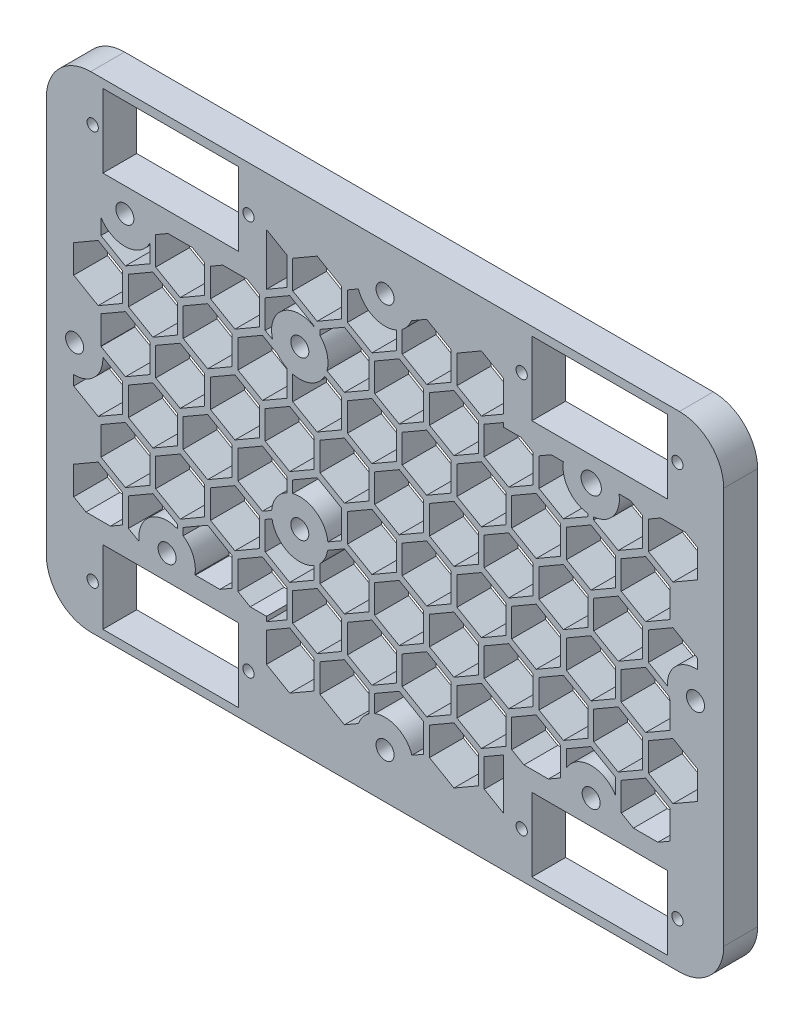
SolidWorks part; units mm, degrees
material "Pin"
ref_plane "Plan de face" through (0, 0, 0) normal (0, 0, 1) x (1, 0, 0)
ref_plane "Plan de dessus" through (0, 0, 0) normal (0, 1, 0) x (1, 0, 0)
ref_plane "Plan de droite" through (0, 0, 0) normal (1, 0, 0) x (0, 0, -1)
sketch "Esquisse1" plane through (0, 0, 0) normal (0, 0, 1) x (1, 0, 0)
  line L0 (-60, -35.145) -> (-60, 35.145)
  line L1 (-52.145, 43) -> (52.145, 43)
  line L2 (-55, 0) -> (-60, 0) construction
  line L3 (55, 0) -> (55, 42.4628) construction
  line L4 (60, -35.145) -> (60, 35.145)
  line L5 (-52.145, -43) -> (52.145, -43)
  line L6 (55, 0) -> (55, -42.4628) construction
  line L7 (-55, 0) -> (-55, -42.4628) construction
  line L8 (-55, 0) -> (-55, 42.4628) construction
  line L9 (55, 0) -> (60, 0) construction
  line L10 (0, -35) -> (59.9987, -35) construction
  line L11 (0, -35) -> (-59.9987, -35) construction
  line L12 (55, 0) -> (60, 0) construction
  line L13 (0, 35) -> (59.9987, 35) construction
  line L14 (0, 35) -> (-59.9987, 35) construction
  arc A0 (60, -35.145) -> (52.145, -43) centre (52.145, -35.145) cw
  arc A1 (-52.145, -43) -> (-60, -35.145) centre (-52.145, -35.145) cw
  circle A2 centre (0, 35) radius 1.6
  circle A3 centre (0, -35) radius 1.6
  arc A4 (-52.145, 43) -> (-60, 35.145) centre (-52.145, 35.145) ccw
  arc A5 (52.145, 43) -> (60, 35.145) centre (52.145, 35.145) cw
  circle A8 centre (-55, 0) radius 1.6
  circle A14 centre (55, 0) radius 1.6
  dimension "D6" = 8
  dimension "D7" = 3.2
  dimension "D8" = 3.2
  dimension "D10" = 120
  dimension "D5" = 5
  dimension "D4" = 86
  dimension "D36" = 3.2
  dimension "D2" = 3.2
extrude "plaque" add sketch "Esquisse1" along normal blind 6 contours L4 L1 L0 A1 L5 A0 region at (0, 0, 0)
sketch "Esquisse3" plane through (0, 0, 0) normal (0, 0, 1) x (1, 0, 0)
  line L0 (0, 0) -> (0, 43.3988) construction
  line L1 (0, 0) -> (-88.517, 0) construction
  line L2 (-51.8, 35) -> (-24.2, 35) construction
  line L3 (26, 28.5) -> (26, 41.5)
  line L4 (-50, 28.5) -> (-50, 41.5)
  line L5 (-50, 28.5) -> (-26, 28.5)
  line L6 (-26, 28.5) -> (-26, 41.5)
  line L7 (-50, 41.5) -> (-26, 41.5)
  line L8 (50, -28.5) -> (26, -28.5)
  line L9 (50, -28.5) -> (50, -41.5)
  line L10 (50, 41.5) -> (26, 41.5)
  line L11 (50, 28.5) -> (50, 41.5)
  line L12 (50, 28.5) -> (26, 28.5)
  line L13 (50, -41.5) -> (26, -41.5)
  line L14 (26, -28.5) -> (26, -41.5)
  line L15 (-51.8, -35) -> (-24.2, -35) construction
  line L16 (-50, -41.5) -> (-26, -41.5)
  line L17 (-26, -28.5) -> (-26, -41.5)
  line L18 (-50, -28.5) -> (-26, -28.5)
  line L19 (-50, -28.5) -> (-50, -41.5)
  circle A0 centre (-51.8, 35) radius 1
  circle A1 centre (-24.2, 35) radius 1
  circle A2 centre (51.8, 35) radius 1
  circle A3 centre (24.2, 35) radius 1
  circle A4 centre (24.2, -35) radius 1
  circle A5 centre (51.8, -35) radius 1
  circle A6 centre (-24.2, -35) radius 1
  circle A7 centre (-51.8, -35) radius 1
  point P3 (-50, 35)
  point P8 (-38, 35)
  point P37 (-26, 35)
  point P40 (-38, -35)
  dimension "D2" = 2
  dimension "D1" = 27.6
  dimension "D3" = 13
  dimension "D4" = 24
  dimension "D5" = 38
  dimension "D6" = 35
  dimension "D7" = 90
  dimension "D8" = 1.8
extrude "MIP_SERVO" cut sketch "Esquisse3" along normal through all
sketch "Sketch1" plane through (0, 0, 0) normal (0, 0, -1) x (-1, 0, 0)
  line L0 (-60, -35.145) -> (-60, 35.145) construction
  line L1 (-55.3301, 23.75) -> (-55.3301, 18.75)
  line L2 (-55.3301, 18.75) -> (-51, 16.25)
  line L3 (-51, 16.25) -> (-46.6699, 18.75)
  line L4 (-46.6699, 18.75) -> (-46.6699, 23.75)
  line L5 (-46.6699, 23.75) -> (-51, 26.25)
  line L6 (-51, 26.25) -> (-55.3301, 23.75)
  line L7 (52.145, 43) -> (-52.145, 43) construction
  line L8 (-50.5, 32.25) -> (-50.5, 27.25)
  line L9 (-50.5, 27.25) -> (-46.1699, 24.75)
  line L10 (-46.1699, 24.75) -> (-41.8397, 27.25)
  line L11 (-41.8397, 27.25) -> (-41.8397, 32.25)
  line L12 (-41.8397, 32.25) -> (-46.1699, 34.75)
  line L13 (-46.1699, 34.75) -> (-50.5, 32.25)
  line L14 (-45.6301, 23.75) -> (-45.6301, 18.75)
  line L15 (-45.6301, 18.75) -> (-41.3, 16.25)
  line L16 (-41.3, 16.25) -> (-36.9699, 18.75)
  line L17 (-36.9699, 18.75) -> (-36.9699, 23.75)
  line L18 (-36.9699, 23.75) -> (-41.3, 26.25)
  line L19 (-41.3, 26.25) -> (-45.6301, 23.75)
  line L20 (-40.8, 32.25) -> (-40.8, 27.25)
  line L21 (-40.8, 27.25) -> (-36.4699, 24.75)
  line L22 (-36.4699, 24.75) -> (-32.1397, 27.25)
  line L23 (-32.1397, 27.25) -> (-32.1397, 32.25)
  line L24 (-32.1397, 32.25) -> (-36.4699, 34.75)
  line L25 (-36.4699, 34.75) -> (-40.8, 32.25)
  line L26 (-35.9301, 23.75) -> (-35.9301, 18.75)
  line L27 (-35.9301, 18.75) -> (-31.6, 16.25)
  line L28 (-31.6, 16.25) -> (-27.2699, 18.75)
  line L29 (-27.2699, 18.75) -> (-27.2699, 23.75)
  line L30 (-27.2699, 23.75) -> (-31.6, 26.25)
  line L31 (-31.6, 26.25) -> (-35.9301, 23.75)
  line L32 (-31.1, 32.25) -> (-31.1, 27.25)
  line L33 (-31.1, 27.25) -> (-26.7699, 24.75)
  line L34 (-26.7699, 24.75) -> (-22.4397, 27.25)
  line L35 (-22.4397, 27.25) -> (-22.4397, 32.25)
  line L36 (-22.4397, 32.25) -> (-26.7699, 34.75)
  line L37 (-26.7699, 34.75) -> (-31.1, 32.25)
  line L38 (-26.2301, 23.75) -> (-26.2301, 18.75)
  line L39 (-26.2301, 18.75) -> (-21.9, 16.25)
  line L40 (-21.9, 16.25) -> (-17.5699, 18.75)
  line L41 (-17.5699, 18.75) -> (-17.5699, 23.75)
  line L42 (-17.5699, 23.75) -> (-21.9, 26.25)
  line L43 (-21.9, 26.25) -> (-26.2301, 23.75)
  line L44 (-21.4, 32.25) -> (-21.4, 27.25)
  line L45 (-21.4, 27.25) -> (-17.0699, 24.75)
  line L46 (-17.0699, 24.75) -> (-12.7397, 27.25)
  line L47 (-12.7397, 27.25) -> (-12.7397, 32.25)
  line L48 (-12.7397, 32.25) -> (-17.0699, 34.75)
  line L49 (-17.0699, 34.75) -> (-21.4, 32.25)
  line L50 (-16.5301, 23.75) -> (-16.5301, 18.75)
  line L51 (-16.5301, 18.75) -> (-12.2, 16.25)
  line L52 (-12.2, 16.25) -> (-7.8699, 18.75)
  line L53 (-7.8699, 18.75) -> (-7.8699, 23.75)
  line L54 (-7.8699, 23.75) -> (-12.2, 26.25)
  line L55 (-12.2, 26.25) -> (-16.5301, 23.75)
  line L56 (-11.7, 32.25) -> (-11.7, 27.25)
  line L57 (-11.7, 27.25) -> (-7.3699, 24.75)
  line L58 (-7.3699, 24.75) -> (-3.0397, 27.25)
  line L59 (-3.0397, 27.25) -> (-3.0397, 32.25)
  line L60 (-3.0397, 32.25) -> (-7.3699, 34.75)
  line L61 (-7.3699, 34.75) -> (-11.7, 32.25)
  line L62 (-6.8301, 23.75) -> (-6.8301, 18.75)
  line L63 (-6.8301, 18.75) -> (-2.5, 16.25)
  line L64 (-2.5, 16.25) -> (1.8301, 18.75)
  line L65 (1.8301, 18.75) -> (1.8301, 23.75)
  line L66 (1.8301, 23.75) -> (-2.5, 26.25)
  line L67 (-2.5, 26.25) -> (-6.8301, 23.75)
  line L68 (-2, 32.25) -> (-2, 27.25)
  line L69 (-2, 27.25) -> (2.3301, 24.75)
  line L70 (2.3301, 24.75) -> (6.6603, 27.25)
  line L71 (6.6603, 27.25) -> (6.6603, 32.25)
  line L72 (6.6603, 32.25) -> (2.3301, 34.75)
  line L73 (2.3301, 34.75) -> (-2, 32.25)
  line L74 (2.8699, 23.75) -> (2.8699, 18.75)
  line L75 (2.8699, 18.75) -> (7.2, 16.25)
  line L76 (7.2, 16.25) -> (11.5301, 18.75)
  line L77 (11.5301, 18.75) -> (11.5301, 23.75)
  line L78 (11.5301, 23.75) -> (7.2, 26.25)
  line L79 (7.2, 26.25) -> (2.8699, 23.75)
  line L80 (7.7, 32.25) -> (7.7, 27.25)
  line L81 (7.7, 27.25) -> (12.0301, 24.75)
  line L82 (12.0301, 24.75) -> (16.3603, 27.25)
  line L83 (16.3603, 27.25) -> (16.3603, 32.25)
  line L84 (16.3603, 32.25) -> (12.0301, 34.75)
  line L85 (12.0301, 34.75) -> (7.7, 32.25)
  line L86 (12.5699, 23.75) -> (12.5699, 18.75)
  line L87 (12.5699, 18.75) -> (16.9, 16.25)
  line L88 (16.9, 16.25) -> (21.2301, 18.75)
  line L89 (21.2301, 18.75) -> (21.2301, 23.75)
  line L90 (21.2301, 23.75) -> (16.9, 26.25)
  line L91 (16.9, 26.25) -> (12.5699, 23.75)
  line L92 (17.4, 32.25) -> (17.4, 27.25)
  line L93 (17.4, 27.25) -> (21.7301, 24.75)
  line L94 (21.7301, 24.75) -> (26.0603, 27.25)
  line L95 (26.0603, 27.25) -> (26.0603, 32.25)
  line L96 (26.0603, 32.25) -> (21.7301, 34.75)
  line L97 (21.7301, 34.75) -> (17.4, 32.25)
  line L98 (22.2699, 23.75) -> (22.2699, 18.75)
  line L99 (22.2699, 18.75) -> (26.6, 16.25)
  line L100 (26.6, 16.25) -> (30.9301, 18.75)
  line L101 (30.9301, 18.75) -> (30.9301, 23.75)
  line L102 (30.9301, 23.75) -> (26.6, 26.25)
  line L103 (26.6, 26.25) -> (22.2699, 23.75)
  line L104 (27.1, 32.25) -> (27.1, 27.25)
  line L105 (27.1, 27.25) -> (31.4301, 24.75)
  line L106 (31.4301, 24.75) -> (35.7603, 27.25)
  line L107 (35.7603, 27.25) -> (35.7603, 32.25)
  line L108 (35.7603, 32.25) -> (31.4301, 34.75)
  line L109 (31.4301, 34.75) -> (27.1, 32.25)
  line L110 (31.9699, 23.75) -> (31.9699, 18.75)
  line L111 (31.9699, 18.75) -> (36.3, 16.25)
  line L112 (36.3, 16.25) -> (40.6301, 18.75)
  line L113 (40.6301, 18.75) -> (40.6301, 23.75)
  line L114 (40.6301, 23.75) -> (36.3, 26.25)
  line L115 (36.3, 26.25) -> (31.9699, 23.75)
  line L116 (36.8, 32.25) -> (36.8, 27.25)
  line L117 (36.8, 27.25) -> (41.1301, 24.75)
  line L118 (41.1301, 24.75) -> (45.4603, 27.25)
  line L119 (45.4603, 27.25) -> (45.4603, 32.25)
  line L120 (45.4603, 32.25) -> (41.1301, 34.75)
  line L121 (41.1301, 34.75) -> (36.8, 32.25)
  line L122 (41.6699, 23.75) -> (41.6699, 18.75)
  line L123 (41.6699, 18.75) -> (46, 16.25)
  line L124 (46, 16.25) -> (50.3301, 18.75)
  line L125 (50.3301, 18.75) -> (50.3301, 23.75)
  line L126 (50.3301, 23.75) -> (46, 26.25)
  line L127 (46, 26.25) -> (41.6699, 23.75)
  line L128 (46.5, 32.25) -> (46.5, 27.25)
  line L129 (46.5, 27.25) -> (50.8301, 24.75)
  line L130 (50.8301, 24.75) -> (55.1603, 27.25)
  line L131 (55.1603, 27.25) -> (55.1603, 32.25)
  line L132 (55.1603, 32.25) -> (50.8301, 34.75)
  line L133 (50.8301, 34.75) -> (46.5, 32.25)
  line L134 (-45.6301, 6.75) -> (-45.6301, 1.75)
  line L135 (-45.6301, 1.75) -> (-41.3, -0.75)
  line L136 (-41.3, -0.75) -> (-36.9699, 1.75)
  line L137 (-36.9699, 1.75) -> (-36.9699, 6.75)
  line L138 (-36.9699, 6.75) -> (-41.3, 9.25)
  line L139 (-41.3, 9.25) -> (-45.6301, 6.75)
  line L140 (-40.8, 15.25) -> (-40.8, 10.25)
  line L141 (-40.8, 10.25) -> (-36.4699, 7.75)
  line L142 (-36.4699, 7.75) -> (-32.1397, 10.25)
  line L143 (-32.1397, 10.25) -> (-32.1397, 15.25)
  line L144 (-32.1397, 15.25) -> (-36.4699, 17.75)
  line L145 (-36.4699, 17.75) -> (-40.8, 15.25)
  line L146 (-35.9301, 6.75) -> (-35.9301, 1.75)
  line L147 (-35.9301, 1.75) -> (-31.6, -0.75)
  line L148 (-31.6, -0.75) -> (-27.2699, 1.75)
  line L149 (-27.2699, 1.75) -> (-27.2699, 6.75)
  line L150 (-27.2699, 6.75) -> (-31.6, 9.25)
  line L151 (-31.6, 9.25) -> (-35.9301, 6.75)
  line L152 (-31.1, 15.25) -> (-31.1, 10.25)
  line L153 (-31.1, 10.25) -> (-26.7699, 7.75)
  line L154 (-26.7699, 7.75) -> (-22.4397, 10.25)
  line L155 (-22.4397, 10.25) -> (-22.4397, 15.25)
  line L156 (-22.4397, 15.25) -> (-26.7699, 17.75)
  line L157 (-26.7699, 17.75) -> (-31.1, 15.25)
  line L158 (-26.2301, 6.75) -> (-26.2301, 1.75)
  line L159 (-26.2301, 1.75) -> (-21.9, -0.75)
  line L160 (-21.9, -0.75) -> (-17.5699, 1.75)
  line L161 (-17.5699, 1.75) -> (-17.5699, 6.75)
  line L162 (-17.5699, 6.75) -> (-21.9, 9.25)
  line L163 (-21.9, 9.25) -> (-26.2301, 6.75)
  line L164 (-21.4, 15.25) -> (-21.4, 10.25)
  line L165 (-21.4, 10.25) -> (-17.0699, 7.75)
  line L166 (-17.0699, 7.75) -> (-12.7397, 10.25)
  line L167 (-12.7397, 10.25) -> (-12.7397, 15.25)
  line L168 (-12.7397, 15.25) -> (-17.0699, 17.75)
  line L169 (-17.0699, 17.75) -> (-21.4, 15.25)
  line L170 (-16.5301, 6.75) -> (-16.5301, 1.75)
  line L171 (-16.5301, 1.75) -> (-12.2, -0.75)
  line L172 (-12.2, -0.75) -> (-7.8699, 1.75)
  line L173 (-7.8699, 1.75) -> (-7.8699, 6.75)
  line L174 (-7.8699, 6.75) -> (-12.2, 9.25)
  line L175 (-12.2, 9.25) -> (-16.5301, 6.75)
  line L176 (-11.7, 15.25) -> (-11.7, 10.25)
  line L177 (-11.7, 10.25) -> (-7.3699, 7.75)
  line L178 (-7.3699, 7.75) -> (-3.0397, 10.25)
  line L179 (-3.0397, 10.25) -> (-3.0397, 15.25)
  line L180 (-3.0397, 15.25) -> (-7.3699, 17.75)
  line L181 (-7.3699, 17.75) -> (-11.7, 15.25)
  line L182 (-6.8301, 6.75) -> (-6.8301, 1.75)
  line L183 (-6.8301, 1.75) -> (-2.5, -0.75)
  line L184 (-2.5, -0.75) -> (1.8301, 1.75)
  line L185 (1.8301, 1.75) -> (1.8301, 6.75)
  line L186 (1.8301, 6.75) -> (-2.5, 9.25)
  line L187 (-2.5, 9.25) -> (-6.8301, 6.75)
  line L188 (-2, 15.25) -> (-2, 10.25)
  line L189 (-2, 10.25) -> (2.3301, 7.75)
  line L190 (2.3301, 7.75) -> (6.6603, 10.25)
  line L191 (6.6603, 10.25) -> (6.6603, 15.25)
  line L192 (6.6603, 15.25) -> (2.3301, 17.75)
  line L193 (2.3301, 17.75) -> (-2, 15.25)
  line L194 (2.8699, 6.75) -> (2.8699, 1.75)
  line L195 (2.8699, 1.75) -> (7.2, -0.75)
  line L196 (7.2, -0.75) -> (11.5301, 1.75)
  line L197 (11.5301, 1.75) -> (11.5301, 6.75)
  line L198 (11.5301, 6.75) -> (7.2, 9.25)
  line L199 (7.2, 9.25) -> (2.8699, 6.75)
  line L200 (7.7, 15.25) -> (7.7, 10.25)
  line L201 (7.7, 10.25) -> (12.0301, 7.75)
  line L202 (12.0301, 7.75) -> (16.3603, 10.25)
  line L203 (16.3603, 10.25) -> (16.3603, 15.25)
  line L204 (16.3603, 15.25) -> (12.0301, 17.75)
  line L205 (12.0301, 17.75) -> (7.7, 15.25)
  line L206 (12.5699, 6.75) -> (12.5699, 1.75)
  line L207 (12.5699, 1.75) -> (16.9, -0.75)
  line L208 (16.9, -0.75) -> (21.2301, 1.75)
  line L209 (21.2301, 1.75) -> (21.2301, 6.75)
  line L210 (21.2301, 6.75) -> (16.9, 9.25)
  line L211 (16.9, 9.25) -> (12.5699, 6.75)
  line L212 (17.4, 15.25) -> (17.4, 10.25)
  line L213 (17.4, 10.25) -> (21.7301, 7.75)
  line L214 (21.7301, 7.75) -> (26.0603, 10.25)
  line L215 (26.0603, 10.25) -> (26.0603, 15.25)
  line L216 (26.0603, 15.25) -> (21.7301, 17.75)
  line L217 (21.7301, 17.75) -> (17.4, 15.25)
  line L218 (22.2699, 6.75) -> (22.2699, 1.75)
  line L219 (22.2699, 1.75) -> (26.6, -0.75)
  line L220 (26.6, -0.75) -> (30.9301, 1.75)
  line L221 (30.9301, 1.75) -> (30.9301, 6.75)
  line L222 (30.9301, 6.75) -> (26.6, 9.25)
  line L223 (26.6, 9.25) -> (22.2699, 6.75)
  line L224 (27.1, 15.25) -> (27.1, 10.25)
  line L225 (27.1, 10.25) -> (31.4301, 7.75)
  line L226 (31.4301, 7.75) -> (35.7603, 10.25)
  line L227 (35.7603, 10.25) -> (35.7603, 15.25)
  line L228 (35.7603, 15.25) -> (31.4301, 17.75)
  line L229 (31.4301, 17.75) -> (27.1, 15.25)
  line L230 (31.9699, 6.75) -> (31.9699, 1.75)
  line L231 (31.9699, 1.75) -> (36.3, -0.75)
  line L232 (36.3, -0.75) -> (40.6301, 1.75)
  line L233 (40.6301, 1.75) -> (40.6301, 6.75)
  line L234 (40.6301, 6.75) -> (36.3, 9.25)
  line L235 (36.3, 9.25) -> (31.9699, 6.75)
  line L236 (36.8, 15.25) -> (36.8, 10.25)
  line L237 (36.8, 10.25) -> (41.1301, 7.75)
  line L238 (41.1301, 7.75) -> (45.4603, 10.25)
  line L239 (45.4603, 10.25) -> (45.4603, 15.25)
  line L240 (45.4603, 15.25) -> (41.1301, 17.75)
  line L241 (41.1301, 17.75) -> (36.8, 15.25)
  line L242 (41.6699, 6.75) -> (41.6699, 1.75)
  line L243 (41.6699, 1.75) -> (46, -0.75)
  line L244 (46, -0.75) -> (50.3301, 1.75)
  line L245 (50.3301, 1.75) -> (50.3301, 6.75)
  line L246 (50.3301, 6.75) -> (46, 9.25)
  line L247 (46, 9.25) -> (41.6699, 6.75)
  line L248 (46.5, 15.25) -> (46.5, 10.25)
  line L249 (46.5, 10.25) -> (50.8301, 7.75)
  line L250 (50.8301, 7.75) -> (55.1603, 10.25)
  line L251 (55.1603, 10.25) -> (55.1603, 15.25)
  line L252 (55.1603, 15.25) -> (50.8301, 17.75)
  line L253 (50.8301, 17.75) -> (46.5, 15.25)
  line L254 (-45.6301, -10.25) -> (-45.6301, -15.25)
  line L255 (-45.6301, -15.25) -> (-41.3, -17.75)
  line L256 (-41.3, -17.75) -> (-36.9699, -15.25)
  line L257 (-36.9699, -15.25) -> (-36.9699, -10.25)
  line L258 (-36.9699, -10.25) -> (-41.3, -7.75)
  line L259 (-41.3, -7.75) -> (-45.6301, -10.25)
  line L260 (-40.8, -1.75) -> (-40.8, -6.75)
  line L261 (-40.8, -6.75) -> (-36.4699, -9.25)
  line L262 (-36.4699, -9.25) -> (-32.1397, -6.75)
  line L263 (-32.1397, -6.75) -> (-32.1397, -1.75)
  line L264 (-32.1397, -1.75) -> (-36.4699, 0.75)
  line L265 (-36.4699, 0.75) -> (-40.8, -1.75)
  line L266 (-35.9301, -10.25) -> (-35.9301, -15.25)
  line L267 (-35.9301, -15.25) -> (-31.6, -17.75)
  line L268 (-31.6, -17.75) -> (-27.2699, -15.25)
  line L269 (-27.2699, -15.25) -> (-27.2699, -10.25)
  line L270 (-27.2699, -10.25) -> (-31.6, -7.75)
  line L271 (-31.6, -7.75) -> (-35.9301, -10.25)
  line L272 (-31.1, -1.75) -> (-31.1, -6.75)
  line L273 (-31.1, -6.75) -> (-26.7699, -9.25)
  line L274 (-26.7699, -9.25) -> (-22.4397, -6.75)
  line L275 (-22.4397, -6.75) -> (-22.4397, -1.75)
  line L276 (-22.4397, -1.75) -> (-26.7699, 0.75)
  line L277 (-26.7699, 0.75) -> (-31.1, -1.75)
  line L278 (-26.2301, -10.25) -> (-26.2301, -15.25)
  line L279 (-26.2301, -15.25) -> (-21.9, -17.75)
  line L280 (-21.9, -17.75) -> (-17.5699, -15.25)
  line L281 (-17.5699, -15.25) -> (-17.5699, -10.25)
  line L282 (-17.5699, -10.25) -> (-21.9, -7.75)
  line L283 (-21.9, -7.75) -> (-26.2301, -10.25)
  line L284 (-21.4, -1.75) -> (-21.4, -6.75)
  line L285 (-21.4, -6.75) -> (-17.0699, -9.25)
  line L286 (-17.0699, -9.25) -> (-12.7397, -6.75)
  line L287 (-12.7397, -6.75) -> (-12.7397, -1.75)
  line L288 (-12.7397, -1.75) -> (-17.0699, 0.75)
  line L289 (-17.0699, 0.75) -> (-21.4, -1.75)
  line L290 (-16.5301, -10.25) -> (-16.5301, -15.25)
  line L291 (-16.5301, -15.25) -> (-12.2, -17.75)
  line L292 (-12.2, -17.75) -> (-7.8699, -15.25)
  line L293 (-7.8699, -15.25) -> (-7.8699, -10.25)
  line L294 (-7.8699, -10.25) -> (-12.2, -7.75)
  line L295 (-12.2, -7.75) -> (-16.5301, -10.25)
  line L296 (-11.7, -1.75) -> (-11.7, -6.75)
  line L297 (-11.7, -6.75) -> (-7.3699, -9.25)
  line L298 (-7.3699, -9.25) -> (-3.0397, -6.75)
  line L299 (-3.0397, -6.75) -> (-3.0397, -1.75)
  line L300 (-3.0397, -1.75) -> (-7.3699, 0.75)
  line L301 (-7.3699, 0.75) -> (-11.7, -1.75)
  line L302 (-6.8301, -10.25) -> (-6.8301, -15.25)
  line L303 (-6.8301, -15.25) -> (-2.5, -17.75)
  line L304 (-2.5, -17.75) -> (1.8301, -15.25)
  line L305 (1.8301, -15.25) -> (1.8301, -10.25)
  line L306 (1.8301, -10.25) -> (-2.5, -7.75)
  line L307 (-2.5, -7.75) -> (-6.8301, -10.25)
  line L308 (-2, -1.75) -> (-2, -6.75)
  line L309 (-2, -6.75) -> (2.3301, -9.25)
  line L310 (2.3301, -9.25) -> (6.6603, -6.75)
  line L311 (6.6603, -6.75) -> (6.6603, -1.75)
  line L312 (6.6603, -1.75) -> (2.3301, 0.75)
  line L313 (2.3301, 0.75) -> (-2, -1.75)
  line L314 (2.8699, -10.25) -> (2.8699, -15.25)
  line L315 (2.8699, -15.25) -> (7.2, -17.75)
  line L316 (7.2, -17.75) -> (11.5301, -15.25)
  line L317 (11.5301, -15.25) -> (11.5301, -10.25)
  line L318 (11.5301, -10.25) -> (7.2, -7.75)
  line L319 (7.2, -7.75) -> (2.8699, -10.25)
  line L320 (7.7, -1.75) -> (7.7, -6.75)
  line L321 (7.7, -6.75) -> (12.0301, -9.25)
  line L322 (12.0301, -9.25) -> (16.3603, -6.75)
  line L323 (16.3603, -6.75) -> (16.3603, -1.75)
  line L324 (16.3603, -1.75) -> (12.0301, 0.75)
  line L325 (12.0301, 0.75) -> (7.7, -1.75)
  line L326 (12.5699, -10.25) -> (12.5699, -15.25)
  line L327 (12.5699, -15.25) -> (16.9, -17.75)
  line L328 (16.9, -17.75) -> (21.2301, -15.25)
  line L329 (21.2301, -15.25) -> (21.2301, -10.25)
  line L330 (21.2301, -10.25) -> (16.9, -7.75)
  line L331 (16.9, -7.75) -> (12.5699, -10.25)
  line L332 (17.4, -1.75) -> (17.4, -6.75)
  line L333 (17.4, -6.75) -> (21.7301, -9.25)
  line L334 (21.7301, -9.25) -> (26.0603, -6.75)
  line L335 (26.0603, -6.75) -> (26.0603, -1.75)
  line L336 (26.0603, -1.75) -> (21.7301, 0.75)
  line L337 (21.7301, 0.75) -> (17.4, -1.75)
  line L374 (22.2699, -10.25) -> (22.2699, -15.25)
  line L375 (22.2699, -15.25) -> (26.6, -17.75)
  line L376 (26.6, -17.75) -> (30.9301, -15.25)
  line L377 (30.9301, -15.25) -> (30.9301, -10.25)
  line L378 (30.9301, -10.25) -> (26.6, -7.75)
  line L379 (26.6, -7.75) -> (22.2699, -10.25)
  line L380 (27.1, -1.75) -> (27.1, -6.75)
  line L381 (27.1, -6.75) -> (31.4301, -9.25)
  line L382 (31.4301, -9.25) -> (35.7603, -6.75)
  line L383 (35.7603, -6.75) -> (35.7603, -1.75)
  line L384 (35.7603, -1.75) -> (31.4301, 0.75)
  line L385 (31.4301, 0.75) -> (27.1, -1.75)
  line L386 (0, 0) -> (-84.9086, 0) construction
  line L387 (-10, -39) -> (-10, -32)
  line L388 (6, 32) -> (6, 39)
  line L389 (-6, -39) -> (-6, -32)
  line L390 (10, 32) -> (10, 39)
  line L391 (10, -32) -> (10, -39)
  line L392 (31.9699, -10.25) -> (31.9699, -15.25)
  line L393 (31.9699, -15.25) -> (36.3, -17.75)
  line L394 (36.3, -17.75) -> (40.6301, -15.25)
  line L395 (40.6301, -15.25) -> (40.6301, -10.25)
  line L396 (40.6301, -10.25) -> (36.3, -7.75)
  line L397 (36.3, -7.75) -> (31.9699, -10.25)
  line L398 (-6, 39) -> (-6, 32)
  line L399 (6, -32) -> (6, -39)
  line L400 (-10, 39) -> (-10, 32)
  line L401 (36.8, -1.75) -> (36.8, -6.75)
  line L402 (36.8, -6.75) -> (41.1301, -9.25)
  line L403 (41.1301, -9.25) -> (45.4603, -6.75)
  line L404 (45.4603, -6.75) -> (45.4603, -1.75)
  line L405 (45.4603, -1.75) -> (41.1301, 0.75)
  line L406 (41.1301, 0.75) -> (36.8, -1.75)
  line L407 (41.6699, -10.25) -> (41.6699, -15.25)
  line L408 (41.6699, -15.25) -> (46, -17.75)
  line L409 (46, -17.75) -> (50.3301, -15.25)
  line L410 (50.3301, -15.25) -> (50.3301, -10.25)
  line L411 (50.3301, -10.25) -> (46, -7.75)
  line L412 (46, -7.75) -> (41.6699, -10.25)
  line L413 (46.5, -1.75) -> (46.5, -6.75)
  line L414 (46.5, -6.75) -> (50.8301, -9.25)
  line L415 (50.8301, -9.25) -> (55.1603, -6.75)
  line L416 (55.1603, -6.75) -> (55.1603, -1.75)
  line L417 (55.1603, -1.75) -> (50.8301, 0.75)
  line L418 (50.8301, 0.75) -> (46.5, -1.75)
  line L419 (-45.6301, -27.25) -> (-45.6301, -32.25)
  line L420 (-45.6301, -32.25) -> (-41.3, -34.75)
  line L421 (-41.3, -34.75) -> (-36.9699, -32.25)
  line L422 (-36.9699, -32.25) -> (-36.9699, -27.25)
  line L423 (-36.9699, -27.25) -> (-41.3, -24.75)
  line L424 (-41.3, -24.75) -> (-45.6301, -27.25)
  line L425 (-40.8, -18.75) -> (-40.8, -23.75)
  line L426 (-40.8, -23.75) -> (-36.4699, -26.25)
  line L427 (-36.4699, -26.25) -> (-32.1397, -23.75)
  line L428 (-32.1397, -23.75) -> (-32.1397, -18.75)
  line L429 (-32.1397, -18.75) -> (-36.4699, -16.25)
  line L430 (-36.4699, -16.25) -> (-40.8, -18.75)
  line L431 (-35.9301, -27.25) -> (-35.9301, -32.25)
  line L432 (-35.9301, -32.25) -> (-31.6, -34.75)
  line L433 (-31.6, -34.75) -> (-27.2699, -32.25)
  line L434 (-27.2699, -32.25) -> (-27.2699, -27.25)
  line L435 (-27.2699, -27.25) -> (-31.6, -24.75)
  line L436 (-31.6, -24.75) -> (-35.9301, -27.25)
  line L437 (-31.1, -18.75) -> (-31.1, -23.75)
  line L438 (-31.1, -23.75) -> (-26.7699, -26.25)
  line L439 (-26.7699, -26.25) -> (-22.4397, -23.75)
  line L440 (-22.4397, -23.75) -> (-22.4397, -18.75)
  line L441 (-22.4397, -18.75) -> (-26.7699, -16.25)
  line L442 (-26.7699, -16.25) -> (-31.1, -18.75)
  line L443 (-26.2301, -27.25) -> (-26.2301, -32.25)
  line L444 (-26.2301, -32.25) -> (-21.9, -34.75)
  line L445 (-21.9, -34.75) -> (-17.5699, -32.25)
  line L488 (-17.5699, -32.25) -> (-17.5699, -27.25)
  line L489 (-17.5699, -27.25) -> (-21.9, -24.75)
  line L490 (-21.9, -24.75) -> (-26.2301, -27.25)
  line L491 (-21.4, -18.75) -> (-21.4, -23.75)
  line L492 (-21.4, -23.75) -> (-17.0699, -26.25)
  line L493 (-17.0699, -26.25) -> (-12.7397, -23.75)
  line L494 (-12.7397, -23.75) -> (-12.7397, -18.75)
  line L495 (-12.7397, -18.75) -> (-17.0699, -16.25)
  line L521 (-17.0699, -16.25) -> (-21.4, -18.75)
  line L522 (-16.5301, -27.25) -> (-16.5301, -32.25)
  line L523 (-16.5301, -32.25) -> (-12.2, -34.75)
  line L524 (-12.2, -34.75) -> (-7.8699, -32.25)
  line L525 (-7.8699, -32.25) -> (-7.8699, -27.25)
  line L526 (-7.8699, -27.25) -> (-12.2, -24.75)
  line L527 (-12.2, -24.75) -> (-16.5301, -27.25)
  line L528 (-11.7, -18.75) -> (-11.7, -23.75)
  line L529 (-11.7, -23.75) -> (-7.3699, -26.25)
  line L530 (-7.3699, -26.25) -> (-3.0397, -23.75)
  line L531 (-3.0397, -23.75) -> (-3.0397, -18.75)
  line L532 (-3.0397, -18.75) -> (-7.3699, -16.25)
  line L533 (-7.3699, -16.25) -> (-11.7, -18.75)
  line L534 (-6.8301, -27.25) -> (-6.8301, -32.25)
  line L535 (-6.8301, -32.25) -> (-2.5, -34.75)
  line L536 (-2.5, -34.75) -> (1.8301, -32.25)
  line L537 (1.8301, -32.25) -> (1.8301, -27.25)
  line L538 (1.8301, -27.25) -> (-2.5, -24.75)
  line L539 (-2.5, -24.75) -> (-6.8301, -27.25)
  line L540 (-2, -18.75) -> (-2, -23.75)
  line L541 (-2, -23.75) -> (2.3301, -26.25)
  line L542 (2.3301, -26.25) -> (6.6603, -23.75)
  line L543 (6.6603, -23.75) -> (6.6603, -18.75)
  line L544 (6.6603, -18.75) -> (2.3301, -16.25)
  line L545 (2.3301, -16.25) -> (-2, -18.75)
  line L546 (2.8699, -27.25) -> (2.8699, -32.25)
  line L547 (2.8699, -32.25) -> (7.2, -34.75)
  line L548 (7.2, -34.75) -> (11.5301, -32.25)
  line L549 (11.5301, -32.25) -> (11.5301, -27.25)
  line L550 (11.5301, -27.25) -> (7.2, -24.75)
  line L551 (7.2, -24.75) -> (2.8699, -27.25)
  line L552 (7.7, -18.75) -> (7.7, -23.75)
  line L553 (7.7, -23.75) -> (12.0301, -26.25)
  line L554 (12.0301, -26.25) -> (16.3603, -23.75)
  line L555 (16.3603, -23.75) -> (16.3603, -18.75)
  line L556 (16.3603, -18.75) -> (12.0301, -16.25)
  line L557 (12.0301, -16.25) -> (7.7, -18.75)
  line L558 (12.5699, -27.25) -> (12.5699, -32.25)
  line L559 (12.5699, -32.25) -> (16.9, -34.75)
  line L560 (16.9, -34.75) -> (21.2301, -32.25)
  line L561 (21.2301, -32.25) -> (21.2301, -27.25)
  line L562 (21.2301, -27.25) -> (16.9, -24.75)
  line L563 (16.9, -24.75) -> (12.5699, -27.25)
  line L564 (17.4, -18.75) -> (17.4, -23.75)
  line L565 (17.4, -23.75) -> (21.7301, -26.25)
  line L566 (21.7301, -26.25) -> (26.0603, -23.75)
  line L567 (26.0603, -23.75) -> (26.0603, -18.75)
  line L568 (26.0603, -18.75) -> (21.7301, -16.25)
  line L569 (21.7301, -16.25) -> (17.4, -18.75)
  line L570 (22.2699, -27.25) -> (22.2699, -32.25)
  line L571 (22.2699, -32.25) -> (26.6, -34.75)
  line L572 (26.6, -34.75) -> (30.9301, -32.25)
  line L573 (30.9301, -32.25) -> (30.9301, -27.25)
  line L574 (30.9301, -27.25) -> (26.6, -24.75)
  line L575 (26.6, -24.75) -> (22.2699, -27.25)
  line L576 (27.1, -18.75) -> (27.1, -23.75)
  line L577 (27.1, -23.75) -> (31.4301, -26.25)
  line L578 (31.4301, -26.25) -> (35.7603, -23.75)
  line L579 (35.7603, -23.75) -> (35.7603, -18.75)
  line L580 (35.7603, -18.75) -> (31.4301, -16.25)
  line L581 (31.4301, -16.25) -> (27.1, -18.75)
  line L582 (31.9699, -27.25) -> (31.9699, -32.25)
  line L583 (31.9699, -32.25) -> (36.3, -34.75)
  line L584 (36.3, -34.75) -> (40.6301, -32.25)
  line L585 (40.6301, -32.25) -> (40.6301, -27.25)
  line L586 (40.6301, -27.25) -> (36.3, -24.75)
  line L587 (36.3, -24.75) -> (31.9699, -27.25)
  line L588 (36.8, -18.75) -> (36.8, -23.75)
  line L589 (36.8, -23.75) -> (41.1301, -26.25)
  line L590 (41.1301, -26.25) -> (45.4603, -23.75)
  line L591 (45.4603, -23.75) -> (45.4603, -18.75)
  line L592 (45.4603, -18.75) -> (41.1301, -16.25)
  line L593 (41.1301, -16.25) -> (36.8, -18.75)
  line L594 (41.6699, -27.25) -> (41.6699, -32.25)
  line L595 (41.6699, -32.25) -> (46, -34.75)
  line L596 (46, -34.75) -> (50.3301, -32.25)
  line L597 (50.3301, -32.25) -> (50.3301, -27.25)
  line L598 (50.3301, -27.25) -> (46, -24.75)
  line L599 (46, -24.75) -> (41.6699, -27.25)
  line L600 (46.5, -18.75) -> (46.5, -23.75)
  line L601 (46.5, -23.75) -> (50.8301, -26.25)
  line L602 (50.8301, -26.25) -> (55.1603, -23.75)
  line L603 (55.1603, -23.75) -> (55.1603, -18.75)
  line L604 (55.1603, -18.75) -> (50.8301, -16.25)
  line L605 (50.8301, -16.25) -> (46.5, -18.75)
  line L606 (-55.3301, 6.75) -> (-55.3301, 1.75)
  line L607 (-55.3301, 1.75) -> (-51, -0.75)
  line L608 (-51, -0.75) -> (-46.6699, 1.75)
  line L609 (-46.6699, 1.75) -> (-46.6699, 6.75)
  line L610 (-46.6699, 6.75) -> (-51, 9.25)
  line L611 (-51, 9.25) -> (-55.3301, 6.75)
  line L612 (-50.5, 15.25) -> (-50.5, 10.25)
  line L613 (-50.5, 10.25) -> (-46.1699, 7.75)
  line L614 (-46.1699, 7.75) -> (-41.8397, 10.25)
  line L615 (-41.8397, 10.25) -> (-41.8397, 15.25)
  line L616 (-41.8397, 15.25) -> (-46.1699, 17.75)
  line L617 (-46.1699, 17.75) -> (-50.5, 15.25)
  line L618 (-55.3301, -10.25) -> (-55.3301, -15.25)
  line L619 (-55.3301, -15.25) -> (-51, -17.75)
  line L620 (-51, -17.75) -> (-46.6699, -15.25)
  line L621 (-46.6699, -15.25) -> (-46.6699, -10.25)
  line L622 (-46.6699, -10.25) -> (-51, -7.75)
  line L623 (-51, -7.75) -> (-55.3301, -10.25)
  line L624 (-50.5, -1.75) -> (-50.5, -6.75)
  line L625 (-50.5, -6.75) -> (-46.1699, -9.25)
  line L626 (-46.1699, -9.25) -> (-41.8397, -6.75)
  line L627 (-41.8397, -6.75) -> (-41.8397, -1.75)
  line L628 (-41.8397, -1.75) -> (-46.1699, 0.75)
  line L629 (-46.1699, 0.75) -> (-50.5, -1.75)
  line L630 (-55.3301, -27.25) -> (-55.3301, -32.25)
  line L631 (-55.3301, -32.25) -> (-51, -34.75)
  line L632 (-51, -34.75) -> (-46.6699, -32.25)
  line L633 (-46.6699, -32.25) -> (-46.6699, -27.25)
  line L634 (-46.6699, -27.25) -> (-51, -24.75)
  line L635 (-51, -24.75) -> (-55.3301, -27.25)
  line L636 (-50.5, -18.75) -> (-50.5, -23.75)
  line L637 (-50.5, -23.75) -> (-46.1699, -26.25)
  line L638 (-46.1699, -26.25) -> (-41.8397, -23.75)
  line L639 (-41.8397, -23.75) -> (-41.8397, -18.75)
  line L640 (-41.8397, -18.75) -> (-46.1699, -16.25)
  line L641 (-46.1699, -16.25) -> (-50.5, -18.75)
  line L643 (52.145, -43) -> (-52.145, -43) construction
  line L645 (-55, -25) -> (-21, -25)
  line L646 (-55, -25) -> (-55, -43)
  line L647 (-55, -43) -> (-21, -43)
  line L648 (-21, -25) -> (-21, -43)
  line L649 (50, -28.5) -> (50, -41.5) construction
  line L650 (21, -43) -> (55, -43)
  line L651 (21, -43) -> (21, -25)
  line L652 (21, -25) -> (55, -25)
  line L653 (-55, 43) -> (-21, 43)
  line L654 (-55, 43) -> (-55, 25)
  line L655 (-55, 25) -> (-21, 25)
  line L656 (-21, 43) -> (-21, 25)
  line L657 (21, 43) -> (55, 43)
  line L658 (21, 43) -> (21, 25)
  line L659 (21, 25) -> (55, 25)
  line L660 (55, 43) -> (55, 25)
  line L661 (-26, -28.5) -> (-26, -41.5) construction
  line L662 (55, -43) -> (55, -25)
  line L663 (-26, 41.5) -> (-26, 28.5) construction
  line L664 (50, 41.5) -> (50, 28.5) construction
  circle A0 centre (-51, 21.25) radius 4.3301 construction
  circle A1 centre (-46.1699, 29.75) radius 4.3301 construction
  circle A2 centre (-41.3, 21.25) radius 4.3301 construction
  circle A3 centre (-36.4699, 29.75) radius 4.3301 construction
  circle A4 centre (-31.6, 21.25) radius 4.3301 construction
  circle A5 centre (-26.7699, 29.75) radius 4.3301 construction
  circle A6 centre (-21.9, 21.25) radius 4.3301 construction
  circle A7 centre (-17.0699, 29.75) radius 4.3301 construction
  circle A8 centre (-12.2, 21.25) radius 4.3301 construction
  circle A9 centre (-7.3699, 29.75) radius 4.3301 construction
  circle A10 centre (-2.5, 21.25) radius 4.3301 construction
  circle A11 centre (16, 35) radius 4
  circle A12 centre (2.3301, 29.75) radius 4.3301 construction
  circle A13 centre (7.2, 21.25) radius 4.3301 construction
  circle A14 centre (12.0301, 29.75) radius 4.3301 construction
  circle A15 centre (16.9, 21.25) radius 4.3301 construction
  circle A16 centre (21.7301, 29.75) radius 4.3301 construction
  circle A17 centre (26.6, 21.25) radius 4.3301 construction
  circle A18 centre (31.4301, 29.75) radius 4.3301 construction
  circle A19 centre (36.3, 21.25) radius 4.3301 construction
  circle A20 centre (41.1301, 29.75) radius 4.3301 construction
  circle A21 centre (-16, 35) radius 4
  circle A22 centre (46, 21.25) radius 4.3301 construction
  circle A23 centre (50.8301, 29.75) radius 4.3301 construction
  circle A24 centre (-41.3, 4.25) radius 4.3301 construction
  circle A25 centre (-36.4699, 12.75) radius 4.3301 construction
  circle A26 centre (-31.6, 4.25) radius 4.3301 construction
  circle A27 centre (-26.7699, 12.75) radius 4.3301 construction
  circle A28 centre (-21.9, 4.25) radius 4.3301 construction
  circle A29 centre (-17.0699, 12.75) radius 4.3301 construction
  circle A30 centre (-12.2, 4.25) radius 4.3301 construction
  circle A31 centre (-7.3699, 12.75) radius 4.3301 construction
  circle A32 centre (-2.5, 4.25) radius 4.3301 construction
  circle A33 centre (2.3301, 12.75) radius 4.3301 construction
  circle A34 centre (7.2, 4.25) radius 4.3301 construction
  circle A35 centre (12.0301, 12.75) radius 4.3301 construction
  circle A36 centre (16.9, 4.25) radius 4.3301 construction
  circle A37 centre (21.7301, 12.75) radius 4.3301 construction
  circle A38 centre (26.6, 4.25) radius 4.3301 construction
  circle A39 centre (31.4301, 12.75) radius 4.3301 construction
  circle A40 centre (36.3, 4.25) radius 4.3301 construction
  arc A41 (10, 39) -> (6, 39) centre (8, 39) ccw
  circle A42 centre (41.1301, 12.75) radius 4.3301 construction
  circle A43 centre (46, 4.25) radius 4.3301 construction
  circle A44 centre (50.8301, 12.75) radius 4.3301 construction
  circle A45 centre (-41.3, -12.75) radius 4.3301 construction
  circle A46 centre (-36.4699, -4.25) radius 4.3301 construction
  arc A47 (10, 32) -> (6, 32) centre (8, 32) cw
  arc A54 (-6, 39) -> (-10, 39) centre (-8, 39) ccw
  arc A55 (-6, 32) -> (-10, 32) centre (-8, 32) cw
  arc A56 (-6, -32) -> (-10, -32) centre (-8, -32) ccw
  arc A57 (-6, -39) -> (-10, -39) centre (-8, -39) cw
  arc A58 (10, -32) -> (6, -32) centre (8, -32) ccw
  arc A59 (10, -39) -> (6, -39) centre (8, -39) cw
  circle A60 centre (-16, -35) radius 4
  circle A61 centre (16, -35) radius 4
  circle A62 centre (-31.6, -12.75) radius 4.3301 construction
  circle A63 centre (-36.5153, 24.2035) radius 1.5
  circle A64 centre (15.1102, 19.325) radius 1.5
  circle A65 centre (46.1109, 24.2035) radius 1.5
  circle A66 centre (15.1102, -8.6912) radius 1.5
  circle A67 centre (-36.5153, -24.1327) radius 1.5
  circle A68 centre (38.6179, -24.1327) radius 1.5
  circle A69 centre (-26.7699, -4.25) radius 4.3301 construction
  circle A70 centre (-21.9, -12.75) radius 4.3301 construction
  circle A71 centre (-17.0699, -4.25) radius 4.3301 construction
  circle A72 centre (-12.2, -12.75) radius 4.3301 construction
  circle A73 centre (-7.3699, -4.25) radius 4.3301 construction
  circle A74 centre (-2.5, -12.75) radius 4.3301 construction
  circle A75 centre (2.3301, -4.25) radius 4.3301 construction
  circle A76 centre (7.2, -12.75) radius 4.3301 construction
  circle A77 centre (12.0301, -4.25) radius 4.3301 construction
  circle A78 centre (16.9, -12.75) radius 4.3301 construction
  circle A79 centre (21.7301, -4.25) radius 4.3301 construction
  circle A80 centre (26.6, -12.75) radius 4.3301 construction
  circle A81 centre (31.4301, -4.25) radius 4.3301 construction
  circle A82 centre (36.3, -12.75) radius 4.3301 construction
  circle A83 centre (41.1301, -4.25) radius 4.3301 construction
  circle A84 centre (46, -12.75) radius 4.3301 construction
  circle A85 centre (50.8301, -4.25) radius 4.3301 construction
  circle A86 centre (-41.3, -29.75) radius 4.3301 construction
  circle A87 centre (-36.4699, -21.25) radius 4.3301 construction
  circle A88 centre (-31.6, -29.75) radius 4.3301 construction
  circle A89 centre (-26.7699, -21.25) radius 4.3301 construction
  circle A90 centre (-21.9, -29.75) radius 4.3301 construction
  circle A91 centre (-17.0699, -21.25) radius 4.3301 construction
  circle A92 centre (-12.2, -29.75) radius 4.3301 construction
  circle A93 centre (-7.3699, -21.25) radius 4.3301 construction
  circle A94 centre (-2.5, -29.75) radius 4.3301 construction
  circle A95 centre (2.3301, -21.25) radius 4.3301 construction
  circle A96 centre (7.2, -29.75) radius 4.3301 construction
  circle A97 centre (12.0301, -21.25) radius 4.3301 construction
  circle A98 centre (16.9, -29.75) radius 4.3301 construction
  circle A99 centre (21.7301, -21.25) radius 4.3301 construction
  circle A100 centre (26.6, -29.75) radius 4.3301 construction
  circle A101 centre (31.4301, -21.25) radius 4.3301 construction
  circle A102 centre (36.3, -29.75) radius 4.3301 construction
  circle A103 centre (41.1301, -21.25) radius 4.3301 construction
  circle A104 centre (46, -29.75) radius 4.3301 construction
  circle A105 centre (50.8301, -21.25) radius 4.3301 construction
  circle A106 centre (-51, 4.25) radius 4.3301 construction
  circle A107 centre (-46.1699, 12.75) radius 4.3301 construction
  circle A108 centre (-51, -12.75) radius 4.3301 construction
  circle A109 centre (-46.1699, -4.25) radius 4.3301 construction
  circle A110 centre (-51, -29.75) radius 4.3301 construction
  circle A111 centre (-46.1699, -21.25) radius 4.3301 construction
  circle A112 centre (55, 0) radius 5
  circle A113 centre (0, 35) radius 5
  circle A114 centre (0, -35) radius 5
  circle A115 centre (-55, 0) radius 5
  circle A116 centre (15.1102, -8.6912) radius 5
  circle A117 centre (15.1102, 19.325) radius 5
  circle A118 centre (38.6179, -24.1327) radius 5
  circle A119 centre (-36.5153, -24.1327) radius 5
  circle A120 centre (-36.5153, 24.2035) radius 5
  circle A121 centre (46.1109, 24.2035) radius 5
  dimension "D2" = 10
  dimension "D3" = 10
  dimension "D4" = 0.5
  dimension "D12" = 3
  dimension "D13" = 3
  dimension "D14" = 3
  dimension "D10" = 8
  dimension "D11" = 8
  dimension "D15" = 3
  dimension "D16" = 3
  dimension "D17" = 3
  dimension "D18" = 10
  dimension "D19" = 10
  dimension "D20" = 10
  dimension "D21" = 10
  dimension "D34" = 10
  dimension "D35" = 10
  dimension "D36" = 10
  dimension "D37" = 10
  dimension "D38" = 10
  dimension "D39" = 10
  dimension "D5" = 1
  dimension "D6" = 13.25
  dimension "D7" = 9
  dimension "D8" = 11
  dimension "D9" = 4
  dimension "D22" = 18
  dimension "D23" = 34
  dimension "D24" = 5
  dimension "D25" = 18
  dimension "D26" = 34
  dimension "D27" = 5
  dimension "D28" = 18
  dimension "D29" = 34
  dimension "D30" = 5
  dimension "D31" = 18
  dimension "D32" = 5
  dimension "D33" = 34
extrude "Cut-Extrude1" cut sketch "Sketch1" against normal blind 10 contours A115 L608 L609 L610 L611 L606 | A115 L624 L625 L626 L627 L628 L629 | L622 L623 L618 L619 L620 L621 | L637 L645 L638 L639 L640 L641 L636 | L616 L617 L612 L613 L614 L615 | L655 L6 L1 L2 L3 L4 L5 | A120 L655 L19 L14 L15 L16 L17 | L144 L145 L140 L141 L142 L143 | L138 L139 L134 L135 L136 L137 | L264 L265 L260 L261 L262 L263 | L258 L259 L254 L255 L256 L257 | A119 L428 L429 L430 L425 | L150 L151 L146 L147 L148 L149 | L156 L157 L152 L153 L154 L155 | A120 L26 L27 L28 L29 L30 L655 | L162 L163 L158 L159 L160 L161 | L276 L277 L272 L273 L274 L275 | L270 L271 L266 L267 L268 L269 | L438 L645 L439 L440 L441 L442 L437 | L445 A60 L488 L489 L648 | L495 L521 L491 L492 L493 L494 | L282 L283 L278 L279 L280 L281 | L288 L289 L284 L285 L286 L287 | L174 L175 L170 L171 L172 L173 | L168 L169 L164 L165 L166 L167 | L42 L656 L655 L43 L38 L39 L40 L41 | L54 L55 L50 L51 L52 L53 | L180 L181 L176 L177 L178 L179 | L186 L187 L182 L183 L184 L185 | L300 L301 L296 L297 L298 L299 | L294 L295 L290 L291 L292 L293 | L532 L533 L528 L529 L530 L531 | L306 L307 L302 L303 L304 L305 | L544 L545 L540 L541 L542 L543 | L312 L313 L308 L309 L310 L311 | A116 L318 L319 L314 L315 L316 L317 | A116 L323 L324 L325 L320 L321 | L198 L199 L194 L195 L196 L197 | L192 L193 L188 L189 L190 L191 | L66 L67 L62 L63 L64 L65 | A113 L68 L69 L70 L71 A47 L388 L72 | A117 L77 L78 L79 L74 L75 L76 | L556 L557 L552 L553 L554 L555 | A116 L326 L327 L328 L329 L330 | L651 L652 L566 L567 L568 L569 L564 L565 | L378 L379 L374 L375 L376 L377 | A116 L333 L334 L335 L336 L337 L332 | L210 L211 L206 L207 L208 L209 | A117 L205 L200 L201 L202 L203 | A117 L212 L213 L214 L215 L216 L217 | L222 L223 L218 L219 L220 L221 | L384 L385 L380 L381 L382 L383 | L396 L397 L392 L393 L394 L395 | L405 L406 L401 L402 L403 L404 | L234 L235 L230 L231 L232 L233 | L228 L229 L224 L225 L226 L227 | L659 L115 L110 L111 L112 L113 L114 | A117 L88 L89 L90 L91 L86 | L659 L103 L98 L99 L100 L101 L102 | L240 L241 L236 L237 L238 L239 | L252 L253 L248 L249 L250 L251 | A121 L122 L123 L124 L125 | A112 L245 L246 L247 L242 L243 L244 | A112 L418 L413 L414 L415 L416 | L411 L412 L407 L408 L409 L410 | L601 L652 L602 L603 L604 L605 L600 | A118 L590 L591 L592 L593 L588 | A118 L579 L580 L581 L576 L577 L652 L578 | A55 L398 L60 L61 L400 | L49 A21 L48 | A47 L390 L85 L80 | L85 A11 L83 L84 | L92 A11 L97 | A47 L71 L72 L388 | A61 L559 L560 | A60 L522 L523 L524 | L391 A58 L399 L547 L548 | L525 A56 L387 L524 | L389 A56 L534 L535 | A60 L445 L488 | L522 A60 L524 L387 A56 L525 L526 L527 | A114 L537 L538 L539 L534 A56 L389 L535 | A114 L547 L399 A58 L391 L548 L549 L550 L551 L546 | L559 A61 L560 L651 L562 L563 L558 | A11 L92 L93 L658 L97 | A21 L49 L656 L45 L46 L47 L48 | A113 L60 L398 A55 L400 L61 L56 L57 L58 L59 | L390 A47 L80 L81 L82 L83 A11 L85 region at (51, 21.0688, 0) region at (17.0757, 28.8703, 0) region at (42.344, 20.4494, 0) region at (16.4581, 32.6654, 0) region at (21.8903, 21.0996, 0) region at (30.5874, 20.4784, 0) region at (12.2, 21.25, 0) region at (7.3088, 28.9259, 0) region at (7.9046, 32.2688, 0) region at (-2.7555, 28.5915, 0) region at (-6.3592, 31.6701, 0) region at (-12.0696, 29.1262, 0) region at (-8.8473, 31.6349, 0) region at (-14.2368, 32.5734, 0) region at (-18.3853, 32.3523, 0) region at (-19.4597, 29.5306, 0) region at (-26.6, 21.0688, 0) region at (-45.9191, 18.7122, 0) region at (-36.3, 21.0688, 0) region at (2.5, 21.25, 0) region at (-6.9096, 21.3361, 0) region at (-11.7637, 12.1873, 0) region at (-18.7518, 23.1441, 0) region at (-21.7552, 12.7317, 0) region at (41.3, 4.25, 0) region at (36.4699, 12.75, 0) region at (31.6, 4.25, 0) region at (26.7699, 12.75, 0) region at (21.9, 4.25, 0) region at (17.0699, 12.75, 0) region at (12.2, 4.25, 0) region at (7.3699, 12.75, 0) region at (2.5, 4.25, 0) region at (-2.3301, 12.75, 0) region at (-7.2, 4.25, 0) region at (-16.9, 4.25, 0) region at (-26.6, 4.25, 0) region at (-31.4301, 12.75, 0) region at (-36.3, 4.25, 0) region at (-41.1301, 12.75, 0) region at (-46, 4.25, 0) region at (-50.0763, -5.0621, 0) region at (-50.8301, 12.75, 0) region at (41.3, -12.75, 0) region at (36.4699, -4.25, 0) region at (31.6, -12.75, 0) region at (26.7699, -4.25, 0) region at (21.9, -12.75, 0) region at (17.0699, -4.25, 0) region at (12.2, -12.75, 0) region at (7.3699, -4.25, 0) region at (2.5, -12.75, 0) region at (-2.3301, -4.25, 0) region at (-7.0922, -12.8084, 0) region at (-11.2788, -3.1403, 0) region at (-17.6219, -14.343, 0) region at (-22.0219, -4.06, 0) region at (-26.6, -12.75, 0) region at (-31.4301, -4.25, 0) region at (12.2027, -29.1117, 0)
sketch "Sketch2" plane through (0, 0, 6) normal (0, 0, 1) x (1, 0, 0)
  circle A0 centre (36.5153, 24.2035) radius 1.8
  circle A1 centre (36.5153, -24.1327) radius 1.6
  circle A2 centre (-15.1102, 19.325) radius 1.6
  circle A3 centre (-15.1102, -8.6912) radius 1.6
  circle A4 centre (-38.6179, -24.1327) radius 1.6
  circle A5 centre (-46.1109, 24.2035) radius 1.6
  arc A6 (31.5792, 25) -> (35.9301, 19.2378) centre (36.5153, 24.2035) ccw construction
  dimension "D1" = 3.2
  dimension "D2" = 3.2
  dimension "D3" = 3.2
  dimension "D4" = 3.2
  dimension "D5" = 3.2
  dimension "D6" = 3.2
extrude "Cut-Extrude2" cut sketch "Sketch2" against normal blind 10
